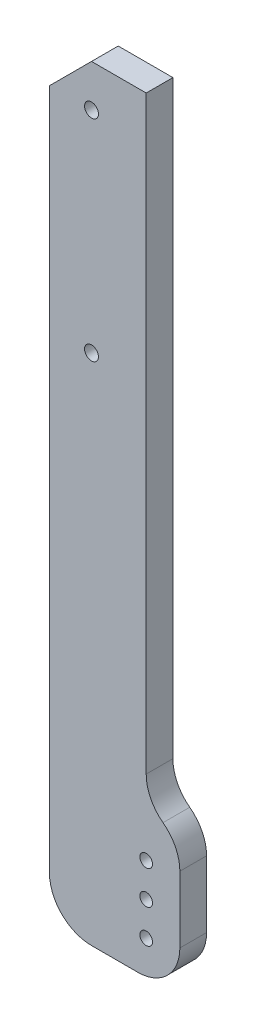
SolidWorks part; units mm, degrees
ref_plane "Front Plane" through (0, 0, 0) normal (0, 0, 1) x (1, 0, 0)
ref_plane "Top Plane" through (0, 0, 0) normal (0, 1, 0) x (1, 0, 0)
ref_plane "Right Plane" through (0, 0, 0) normal (1, 0, 0) x (0, 0, -1)
sketch "Sketch1" plane through (0, 0, 0) normal (0, 0, 1) x (1, 0, 0)
  line L1 (-8, 16) -> (8, 16)
  line L2 (-8, 16) -> (-8, -16)
  line L3 (-8, -16) -> (8, -16)
  line L4 (8, 16) -> (8, -16)
  line L5 (-8, 16) -> (8, -16) construction
  line L6 (-8, -16) -> (8, 16) construction
  line L7 (-8, 16) -> (0, 16)
  line L8 (-8, 16) -> (-8, 166)
  line L9 (-8, 166) -> (0, 166)
  line L10 (0, 16) -> (0, 166)
  line L11 (-8, -16) -> (-23, -16)
  line L12 (-8, -16) -> (-8, 166)
  line L13 (-8, 166) -> (-23, 166)
  line L14 (-23, -16) -> (-23, 166)
  circle A0 centre (0, 0) radius 1.5
  circle A1 centre (0, 8) radius 1.5
  circle A2 centre (0, -8) radius 1.5
  dimension "D1" = 3
  dimension "D2" = 3
  dimension "D3" = 3
  dimension "D4" = 8
  dimension "D5" = 8
  dimension "D6" = 32
  dimension "D7" = 16
  dimension "D8" = 150
  dimension "D9" = 15
extrude "Boss-Extrude1" add sketch "Sketch1" along normal blind 6.35 contours L4 L1 L2 L3 A2 A1 A0 | L1 L10 L9 L8 | L14 L11 L2 L8 L13 region at (-4, 91, 0) region at (-4, 15.6422, 0) region at (-15.5, 75, 0)
fillet "Fillet1" radius 10 3 edges at (8, -16, 3.175) (-23, -16, 3.175) (0, 16, 3.175)
fillet "Fillet2" radius 10 1 edges at (8, 16, 3.175)
chamfer "Chamfer1" distance 10 angle 45 1 edges at (-23, 166, 3.175)
sketch "Sketch2" plane through (0, 0, 6.35) normal (0, 0, 1) x (1, 0, 0)
  line L0 (0, 166) -> (-13, 166) construction
  circle A0 centre (-13, 156) radius 1.65
  circle A1 centre (-13, 106) radius 1.65
  dimension "D1" = 3.3
  dimension "D2" = 3.3
  dimension "D3" = 50
  dimension "D4" = 10
extrude "Cut-Extrude1" cut sketch "Sketch2" against normal blind 10
